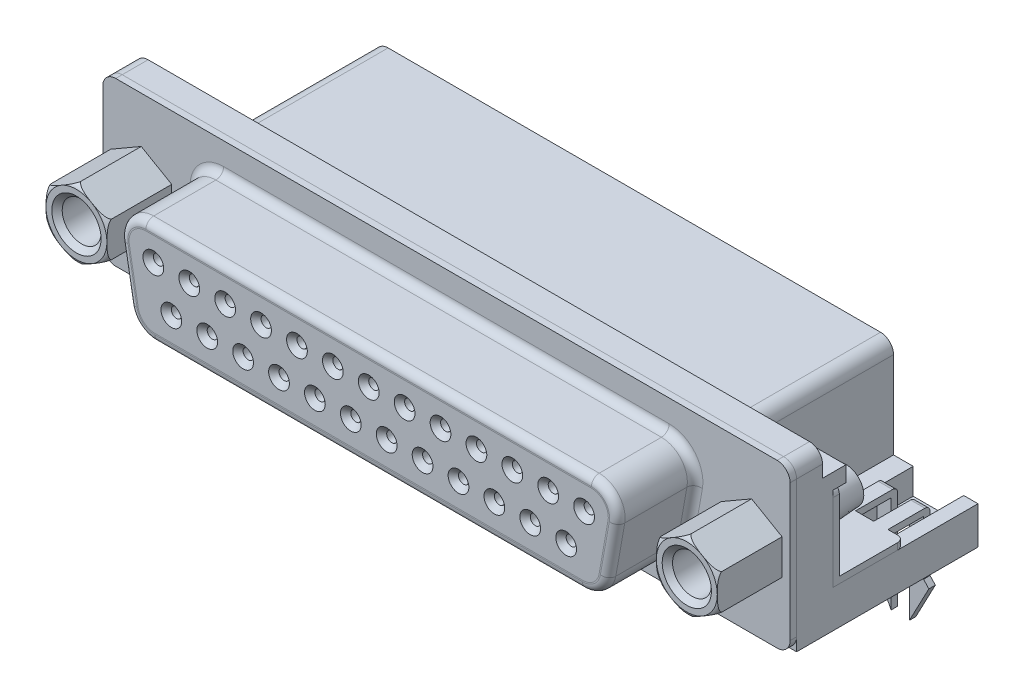
SolidWorks part; units mm, degrees
ref_plane "Alzado" through (0, 0, 0) normal (0, 0, 1) x (1, 0, 0)
ref_plane "Planta" through (0, 0, 0) normal (0, 1, 0) x (1, 0, 0)
ref_plane "Vista lateral" through (0, 0, 0) normal (1, 0, 0) x (0, 0, -1)
sketch "Croquis1" plane through (0, 0, 0) normal (0, 0, 1) x (1, 0, 0)
  line L1 (-25.52, 6.275) -> (25.52, 6.275)
  line L2 (-26.52, 5.275) -> (-26.52, -5.275)
  line L3 (-25.52, -6.275) -> (25.52, -6.275)
  line L4 (26.52, 5.275) -> (26.52, -5.275)
  arc A0 (25.52, 6.275) -> (26.52, 5.275) centre (25.52, 5.275) cw
  arc A1 (25.52, -6.275) -> (26.52, -5.275) centre (25.52, -5.275) ccw
  arc A2 (-25.52, 6.275) -> (-26.52, 5.275) centre (-25.52, 5.275) ccw
  arc A3 (-26.52, -5.275) -> (-25.52, -6.275) centre (-25.52, -5.275) ccw
  point P7 (26.52, 6.275)
  point P12 (-26.52, 6.275)
  dimension "D5" = 1
  dimension "D1" = 53.04
  dimension "D2" = 12.55
  dimension "D3" = 26.52
  dimension "D4" = 6.275
extrude "Extruir1" add sketch "Croquis1" along normal blind 0.5
sketch "Croquis2" plane through (0, 0, 0.5) normal (0, 0, 1) x (1, 0, 0)
  line L0 (19.1596, 1.6027) -> (18.4719, -2.2973)
  line L1 (-17.19, 3.95) -> (17.19, 3.95)
  line L2 (0, 0) -> (0, -16.7466) construction
  line L3 (-16.5023, -3.95) -> (16.5023, -3.95)
  line L4 (-19.1596, 1.6027) -> (-18.4719, -2.2973)
  arc A0 (19.1596, 1.6027) -> (17.19, 3.95) centre (17.19, 1.95) ccw
  arc A1 (-16.5023, -3.95) -> (-18.4719, -2.2973) centre (-16.5023, -1.95) cw
  arc A2 (-19.1596, 1.6027) -> (-17.19, 3.95) centre (-17.19, 1.95) cw
  arc A3 (16.5023, -3.95) -> (18.4719, -2.2973) centre (16.5023, -1.95) ccw
  dimension "D5" = 4
  dimension "D3" = 7.9
  dimension "D4" = 3.95
extrude "Extruir2" add sketch "Croquis2" along normal blind 6
sketch "Croquis3" plane through (0, 0, 6.5) normal (0, 0, 1) x (1, 0, 0)
  line L0 (17.19, 3.25) -> (-17.19, 3.25)
  line L1 (-18.4703, 1.7243) -> (-17.7826, -2.1757)
  line L2 (-16.5023, -3.25) -> (16.5023, -3.25)
  line L3 (17.7826, -2.1757) -> (18.4703, 1.7243)
  arc A0 (-17.19, 3.25) -> (-18.4703, 1.7243) centre (-17.19, 1.95) ccw
  arc A1 (-17.7826, -2.1757) -> (-16.5023, -3.25) centre (-16.5023, -1.95) ccw
  arc A2 (16.5023, -3.25) -> (17.7826, -2.1757) centre (16.5023, -1.95) ccw
  arc A3 (18.4703, 1.7243) -> (17.19, 3.25) centre (17.19, 1.95) ccw
extrude "Cortar-Extruir1" cut sketch "Croquis3" against normal blind 6
fillet "Redondeo1" radius 0.6 16 edges at (18.7221, 3.2356, 0.5) (18.8158, -0.3473, 0.5) (17.7879, -3.4821, 0.5) (0, -3.95, 0.5) (-17.7879, -3.4821, 0.5) (-18.8158, -0.3473, 0.5) (-18.7221, 3.2356, 0.5) (18.7221, 3.2356, 6.5) (18.8158, -0.3473, 6.5) (17.7879, -3.4821, 6.5) (0, -3.95, 6.5) (-17.7879, -3.4821, 6.5) (-18.8158, -0.3473, 6.5) (-18.7221, 3.2356, 6.5) (0, 3.95, 0.5) (0, 3.95, 6.5)
sketch "Croquis5" plane through (0, 0, 0.5) normal (0, 0, 1) x (1, 0, 0)
  line L4 (17.19, 3.25) -> (-17.19, 3.25)
  line L5 (-18.4703, 1.7243) -> (-17.7826, -2.1757)
  line L6 (-16.5023, -3.25) -> (16.5023, -3.25)
  line L7 (17.7826, -2.1757) -> (18.4703, 1.7243)
  line L8 (17.19, 3.25) -> (-17.19, 3.25)
  line L9 (-18.4703, 1.7243) -> (-17.7826, -2.1757)
  line L10 (-16.5023, -3.25) -> (16.5023, -3.25)
  line L11 (17.7826, -2.1757) -> (18.4703, 1.7243)
  circle A0 centre (16.625, 1.42) radius 0.4
  circle A1 centre (13.855, 1.42) radius 0.4
  circle A2 centre (11.085, 1.42) radius 0.4
  circle A3 centre (8.315, 1.42) radius 0.4
  arc A4 (18.4703, 1.7243) -> (17.19, 3.25) centre (17.19, 1.95) ccw
  arc A5 (-17.19, 3.25) -> (-18.4703, 1.7243) centre (-17.19, 1.95) ccw
  arc A6 (-17.7826, -2.1757) -> (-16.5023, -3.25) centre (-16.5023, -1.95) ccw
  arc A7 (16.5023, -3.25) -> (17.7826, -2.1757) centre (16.5023, -1.95) ccw
  arc A8 (18.4703, 1.7243) -> (17.19, 3.25) centre (17.19, 1.95) ccw
  arc A9 (-17.19, 3.25) -> (-18.4703, 1.7243) centre (-17.19, 1.95) ccw
  arc A10 (-17.7826, -2.1757) -> (-16.5023, -3.25) centre (-16.5023, -1.95) ccw
  arc A11 (16.5023, -3.25) -> (17.7826, -2.1757) centre (16.5023, -1.95) ccw
  circle A12 centre (5.545, 1.42) radius 0.4
  circle A13 centre (2.775, 1.42) radius 0.4
  circle A14 centre (0.005, 1.42) radius 0.4
  circle A15 centre (-2.765, 1.42) radius 0.4
  circle A16 centre (-5.535, 1.42) radius 0.4
  circle A17 centre (-8.305, 1.42) radius 0.4
  circle A18 centre (-11.075, 1.42) radius 0.4
  circle A19 centre (-13.845, 1.42) radius 0.4
  circle A20 centre (-16.615, 1.42) radius 0.4
  circle A21 centre (15.24, -1.42) radius 0.4
  circle A22 centre (12.47, -1.42) radius 0.4
  circle A23 centre (9.7, -1.42) radius 0.4
  circle A24 centre (6.93, -1.42) radius 0.4
  circle A25 centre (4.16, -1.42) radius 0.4
  circle A26 centre (1.39, -1.42) radius 0.4
  circle A27 centre (-1.38, -1.42) radius 0.4
  circle A28 centre (-4.15, -1.42) radius 0.4
  circle A29 centre (-6.92, -1.42) radius 0.4
  circle A30 centre (-9.69, -1.42) radius 0.4
  circle A31 centre (-12.46, -1.42) radius 0.4
  circle A32 centre (-15.23, -1.42) radius 0.4
  dimension "D2" = 0.8
  dimension "D3" = 16.625
  dimension "D4" = 1.42
  dimension "D1" = 0
extrude "Extruir3" add sketch "Croquis5" along normal blind 6 separate body
chamfer "Chaflán1" distance 0.4 angle 45 25 edges at (17.025, 1.42, 6.5) (14.255, 1.42, 6.5) (15.64, -1.42, 6.5) (12.87, -1.42, 6.5) (10.1, -1.42, 6.5) (11.485, 1.42, 6.5) (8.715, 1.42, 6.5) (5.945, 1.42, 6.5) (7.33, -1.42, 6.5) (4.56, -1.42, 6.5) (3.175, 1.42, 6.5) (0.405, 1.42, 6.5) (1.79, -1.42, 6.5) (-0.98, -1.42, 6.5) (-2.365, 1.42, 6.5) (-5.135, 1.42, 6.5) (-3.75, -1.42, 6.5) (-6.52, -1.42, 6.5) (-7.905, 1.42, 6.5) (-9.29, -1.42, 6.5) (-10.675, 1.42, 6.5) (-13.445, 1.42, 6.5) (-12.06, -1.42, 6.5) (-14.83, -1.42, 6.5) (-16.215, 1.42, 6.5)
sketch "Croquis6" plane through (0, 0, 0.5) normal (0, 0, 1) x (1, 0, 0)
  circle A0 centre (23.55, 0) radius 1.6
  circle A1 centre (-23.55, 0) radius 1.6
  dimension "D1" = 3.2
  dimension "D2" = 3.2
  dimension "D3" = 23.55
  dimension "D4" = 47.1
extrude "Cortar-Extruir2" cut sketch "Croquis6" against normal blind 6
sketch "Croquis7" plane through (0, 0, 0.5) normal (0, 0, 1) x (1, 0, 0)
  line L1 (23.55, 2.7135) -> (21.2, 1.3568)
  line L2 (21.2, 1.3568) -> (21.2, -1.3568)
  line L3 (21.2, -1.3568) -> (23.55, -2.7135)
  line L4 (23.55, -2.7135) -> (25.9, -1.3568)
  line L5 (25.9, -1.3568) -> (25.9, 1.3568)
  line L6 (25.9, 1.3568) -> (23.55, 2.7135)
  circle A0 centre (23.55, 0) radius 2.35 construction
extrude "Extruir4" add sketch "Croquis7" along normal blind 5 separate body
ref_plane "Plano1" through (23.55, 0, 0) normal (1, 0, 0) x (0, 0, -1)
sketch "Croquis8" plane through (23.55, 0, 0) normal (1, 0, 0) x (0, 0, -1)
  line L0 (-5.5, 1.3568) -> (-5.5, 2.7135) construction
  line L1 (-5.5, 2.7135) -> (-0.5, 2.7135) construction
  line L2 (-5.163, 2.7135) -> (-5.163, 5.0853)
  line L3 (-5.163, 5.0853) -> (-6.4864, 5.0853)
  line L4 (-6.4864, 5.0853) -> (-6.1878, 2.35)
  line L5 (-6.1878, 2.35) -> (-5.5, 2.35)
  line L6 (0, 0) -> (1.3514, 0) construction
  arc A0 (-5.5, 2.35) -> (-5.163, 2.7135) centre (-4.9764, 2.2026) cw
  dimension "D1" = 2.35
revolve "Cortar-Revolución1" cut sketch "Croquis8" angle 360 about L6
sketch "Croquis9" plane through (0, 0, 5.5) normal (0, 0, 1) x (1, 0, 0)
  circle A0 centre (23.55, 0) radius 1.5
  dimension "D1" = 3
extrude "Cortar-Extruir3" cut sketch "Croquis9" against normal blind 4
chamfer "Chaflán2" distance 0.4 angle 45 1 edges at (25.05, 0, 5.5)
mirror "Simetría1" about plane through (0, 0, 0) normal (1, 0, 0) of bodies 108
sketch "Croquis10" plane through (0, 0, 0) normal (0, 0, -1) x (-1, 0, 0)
  line L1 (-25.52, 6.275) -> (25.52, 6.275)
  line L2 (-26.52, 5.275) -> (-26.52, -6.275)
  line L3 (-26.52, -6.275) -> (26.52, -6.275)
  line L4 (26.52, 5.275) -> (26.52, -6.275)
  arc A0 (-25.52, 6.275) -> (-26.52, 5.275) centre (-25.52, 5.275) ccw
  arc A1 (25.52, 6.275) -> (26.52, 5.275) centre (25.52, 5.275) cw
  dimension "D1" = 1
extrude "Extruir5" add sketch "Croquis10" along normal blind 14 separate body
sketch "Croquis11" plane through (0, 0, -14) normal (0, 0, -1) x (-1, 0, 0)
  line L0 (30.0293, -3.375) -> (20, -3.375)
  line L1 (20, -3.375) -> (20, 4.325)
  line L2 (20, 4.325) -> (-20, 4.325)
  line L3 (-20, 4.325) -> (-20, -3.375)
  line L4 (-20, -3.375) -> (-30.6506, -3.375)
  line L5 (-30.6506, -3.375) -> (-30.6506, 10.8258)
  line L6 (-30.6506, 10.8258) -> (30.0293, 10.8258)
  line L7 (30.0293, 10.8258) -> (30.0293, -3.375)
  line L8 (-26.52, -6.275) -> (26.52, -6.275) construction
  dimension "D1" = 40
  dimension "D2" = 20
  dimension "D3" = 2.9
  dimension "D4" = 2.9
  dimension "D5" = 7.7
extrude "Cortar-Extruir4" cut sketch "Croquis11" against normal blind 12
fillet "Redondeo2" radius 1 2 edges at (-20, 4.325, -8) (20, 4.325, -8)
sketch "Croquis12" plane through (26.52, 0, 0) normal (1, 0, 0) x (0, 0, -1)
  line L0 (2, 4.325) -> (3.8, 4.325)
  line L1 (2, 4.325) -> (14, 4.325) construction
  line L2 (3.8, 4.325) -> (3.8, 3.125)
  line L3 (3.8, 3.125) -> (2.8, 3.125)
  line L4 (2.8, 3.125) -> (2.8, -3.375)
  line L5 (14, -3.375) -> (2, -3.375) construction
  line L6 (2.8, -3.375) -> (2, -3.375)
  line L7 (2, -3.375) -> (2, 4.325)
  dimension "D1" = 1.8
  dimension "D2" = 1
  dimension "D3" = 1.2
extrude "Extruir6" add sketch "Croquis12" against normal up to surface (53.04 mm away) separate body up to face at (-26.52, -1.4583, -5.3333)
combine bodies "Combinar1" operation type add bodies to combine 111 112
sketch "Croquis13" plane through (0, -3.375, 0) normal (0, 1, 0) x (-1, 0, 0)
  line L0 (-20, -2.8) -> (-26.52, -2.8) construction
  line L1 (-25.42, -2.8) -> (-21.52, -2.8)
  line L2 (-25.42, -2.8) -> (-25.42, -16.797)
  line L3 (-25.42, -16.797) -> (-21.52, -16.797)
  line L4 (-21.52, -2.8) -> (-21.52, -16.797)
  line L5 (-26.52, -14) -> (-26.52, -2.8) construction
  line L6 (0, 0) -> (0, -26.0275) construction
  line L7 (21.52, -2.8) -> (21.52, -16.797)
  line L8 (25.42, -16.797) -> (21.52, -16.797)
  line L9 (25.42, -2.8) -> (25.42, -16.797)
  line L10 (25.42, -2.8) -> (21.52, -2.8)
  dimension "D1" = 1.1
  dimension "D2" = 3.9
extrude "Cortar-Extruir5" cut sketch "Croquis13" against normal blind 2
sketch "Croquis14" plane through (0, -6.275, 0) normal (0, -1, 0) x (1, 0, 0)
  line L0 (21.52, -14) -> (25.42, -14) construction
  line L1 (19.75, -15.6683) -> (-19.75, -15.6683)
  line L2 (19.75, -15.6683) -> (19.75, -2)
  line L3 (19.75, -2) -> (-19.75, -2)
  line L4 (-19.75, -15.6683) -> (-19.75, -2)
  point P4 (23.47, -14)
  dimension "D1" = 39.5
  dimension "D2" = 12
  dimension "D3" = 19.75
extrude "Cortar-Extruir6" cut sketch "Croquis14" against normal blind 0.6
sketch "Croquis15" plane through (0, -5.675, 0) normal (0, -1, 0) x (1, 0, 0)
  line L0 (16.975, -12.35) -> (16.275, -12.35) construction
  line L1 (16.975, -12) -> (16.275, -12)
  line L2 (16.975, -12) -> (16.975, -12.7)
  line L3 (16.975, -12.7) -> (16.275, -12.7)
  line L4 (16.275, -12) -> (16.275, -12.7)
  line L5 (16.625, -12) -> (16.625, -12.7) construction
  line L6 (19.75, -14) -> (-19.75, -14) construction
  line L7 (14.205, -12) -> (13.505, -12)
  line L8 (14.205, -12) -> (14.205, -12.7)
  line L9 (14.205, -12.7) -> (13.505, -12.7)
  line L10 (13.505, -12) -> (13.505, -12.7)
  line L11 (14.205, -12.35) -> (13.505, -12.35) construction
  line L12 (13.855, -12) -> (13.855, -12.7) construction
  line L13 (11.435, -12) -> (10.735, -12)
  line L14 (11.435, -12) -> (11.435, -12.7)
  line L15 (11.435, -12.7) -> (10.735, -12.7)
  line L16 (10.735, -12) -> (10.735, -12.7)
  line L17 (11.435, -12.35) -> (10.735, -12.35) construction
  line L18 (11.085, -12) -> (11.085, -12.7) construction
  line L19 (8.665, -12) -> (7.965, -12)
  line L20 (8.665, -12) -> (8.665, -12.7)
  line L21 (8.665, -12.7) -> (7.965, -12.7)
  line L22 (7.965, -12) -> (7.965, -12.7)
  line L23 (8.665, -12.35) -> (7.965, -12.35) construction
  line L24 (8.315, -12) -> (8.315, -12.7) construction
  line L25 (5.895, -12) -> (5.195, -12)
  line L26 (5.895, -12) -> (5.895, -12.7)
  line L27 (5.895, -12.7) -> (5.195, -12.7)
  line L28 (5.195, -12) -> (5.195, -12.7)
  line L29 (5.895, -12.35) -> (5.195, -12.35) construction
  line L30 (5.545, -12) -> (5.545, -12.7) construction
  line L31 (3.125, -12) -> (2.425, -12)
  line L32 (3.125, -12) -> (3.125, -12.7)
  line L33 (3.125, -12.7) -> (2.425, -12.7)
  line L34 (2.425, -12) -> (2.425, -12.7)
  line L35 (3.125, -12.35) -> (2.425, -12.35) construction
  line L36 (2.775, -12) -> (2.775, -12.7) construction
  line L37 (0.355, -12) -> (-0.345, -12)
  line L38 (0.355, -12) -> (0.355, -12.7)
  line L39 (0.355, -12.7) -> (-0.345, -12.7)
  line L40 (-0.345, -12) -> (-0.345, -12.7)
  line L41 (0.355, -12.35) -> (-0.345, -12.35) construction
  line L42 (0.005, -12) -> (0.005, -12.7) construction
  line L43 (-2.415, -12) -> (-3.115, -12)
  line L44 (-2.415, -12) -> (-2.415, -12.7)
  line L45 (-2.415, -12.7) -> (-3.115, -12.7)
  line L46 (-3.115, -12) -> (-3.115, -12.7)
  line L47 (-2.415, -12.35) -> (-3.115, -12.35) construction
  line L48 (-2.765, -12) -> (-2.765, -12.7) construction
  line L49 (-5.185, -12) -> (-5.885, -12)
  line L50 (-5.185, -12) -> (-5.185, -12.7)
  line L51 (-5.185, -12.7) -> (-5.885, -12.7)
  line L52 (-5.885, -12) -> (-5.885, -12.7)
  line L53 (-5.185, -12.35) -> (-5.885, -12.35) construction
  line L54 (-5.535, -12) -> (-5.535, -12.7) construction
  line L55 (-7.955, -12) -> (-8.655, -12)
  line L56 (-7.955, -12) -> (-7.955, -12.7)
  line L57 (-7.955, -12.7) -> (-8.655, -12.7)
  line L58 (-8.655, -12) -> (-8.655, -12.7)
  line L59 (-7.955, -12.35) -> (-8.655, -12.35) construction
  line L60 (-8.305, -12) -> (-8.305, -12.7) construction
  line L61 (-10.725, -12) -> (-11.425, -12)
  line L62 (-10.725, -12) -> (-10.725, -12.7)
  line L63 (-10.725, -12.7) -> (-11.425, -12.7)
  line L64 (-11.425, -12) -> (-11.425, -12.7)
  line L65 (-10.725, -12.35) -> (-11.425, -12.35) construction
  line L66 (-11.075, -12) -> (-11.075, -12.7) construction
  line L67 (-13.495, -12) -> (-14.195, -12)
  line L68 (-13.495, -12) -> (-13.495, -12.7)
  line L69 (-13.495, -12.7) -> (-14.195, -12.7)
  line L70 (-14.195, -12) -> (-14.195, -12.7)
  line L71 (-13.495, -12.35) -> (-14.195, -12.35) construction
  line L72 (-13.845, -12) -> (-13.845, -12.7) construction
  line L73 (-16.265, -12) -> (-16.965, -12)
  line L74 (-16.265, -12) -> (-16.265, -12.7)
  line L75 (-16.265, -12.7) -> (-16.965, -12.7)
  line L76 (-16.965, -12) -> (-16.965, -12.7)
  line L77 (-16.265, -12.35) -> (-16.965, -12.35) construction
  line L78 (-16.615, -12) -> (-16.615, -12.7) construction
  line L79 (15.59, -9.86) -> (14.89, -9.86)
  line L80 (15.59, -9.16) -> (15.59, -9.86)
  line L81 (15.24, -9.16) -> (15.24, -9.86) construction
  line L82 (15.59, -9.51) -> (14.89, -9.51) construction
  line L83 (15.59, -9.16) -> (14.89, -9.16)
  line L84 (14.89, -9.16) -> (14.89, -9.86)
  line L85 (12.82, -9.86) -> (12.12, -9.86)
  line L86 (12.82, -9.16) -> (12.82, -9.86)
  line L87 (12.82, -9.16) -> (12.12, -9.16)
  line L88 (12.12, -9.16) -> (12.12, -9.86)
  line L89 (12.47, -9.16) -> (12.47, -9.86) construction
  line L90 (12.82, -9.51) -> (12.12, -9.51) construction
  line L91 (10.05, -9.86) -> (9.35, -9.86)
  line L92 (10.05, -9.16) -> (10.05, -9.86)
  line L93 (10.05, -9.16) -> (9.35, -9.16)
  line L94 (9.35, -9.16) -> (9.35, -9.86)
  line L95 (9.7, -9.16) -> (9.7, -9.86) construction
  line L96 (10.05, -9.51) -> (9.35, -9.51) construction
  line L97 (7.28, -9.86) -> (6.58, -9.86)
  line L98 (7.28, -9.16) -> (7.28, -9.86)
  line L99 (7.28, -9.16) -> (6.58, -9.16)
  line L100 (6.58, -9.16) -> (6.58, -9.86)
  line L101 (6.93, -9.16) -> (6.93, -9.86) construction
  line L102 (7.28, -9.51) -> (6.58, -9.51) construction
  line L103 (4.51, -9.86) -> (3.81, -9.86)
  line L104 (4.51, -9.16) -> (4.51, -9.86)
  line L105 (4.51, -9.16) -> (3.81, -9.16)
  line L106 (3.81, -9.16) -> (3.81, -9.86)
  line L107 (4.16, -9.16) -> (4.16, -9.86) construction
  line L108 (4.51, -9.51) -> (3.81, -9.51) construction
  line L109 (1.74, -9.86) -> (1.04, -9.86)
  line L110 (1.74, -9.16) -> (1.74, -9.86)
  line L111 (1.74, -9.16) -> (1.04, -9.16)
  line L112 (1.04, -9.16) -> (1.04, -9.86)
  line L113 (1.39, -9.16) -> (1.39, -9.86) construction
  line L114 (1.74, -9.51) -> (1.04, -9.51) construction
  line L115 (-1.03, -9.86) -> (-1.73, -9.86)
  line L116 (-1.03, -9.16) -> (-1.03, -9.86)
  line L117 (-1.03, -9.16) -> (-1.73, -9.16)
  line L118 (-1.73, -9.16) -> (-1.73, -9.86)
  line L119 (-1.38, -9.16) -> (-1.38, -9.86) construction
  line L120 (-1.03, -9.51) -> (-1.73, -9.51) construction
  line L121 (-3.8, -9.86) -> (-4.5, -9.86)
  line L122 (-3.8, -9.16) -> (-3.8, -9.86)
  line L123 (-3.8, -9.16) -> (-4.5, -9.16)
  line L124 (-4.5, -9.16) -> (-4.5, -9.86)
  line L125 (-4.15, -9.16) -> (-4.15, -9.86) construction
  line L126 (-3.8, -9.51) -> (-4.5, -9.51) construction
  line L127 (-6.57, -9.86) -> (-7.27, -9.86)
  line L128 (-6.57, -9.16) -> (-6.57, -9.86)
  line L129 (-6.57, -9.16) -> (-7.27, -9.16)
  line L130 (-7.27, -9.16) -> (-7.27, -9.86)
  line L131 (-6.92, -9.16) -> (-6.92, -9.86) construction
  line L132 (-6.57, -9.51) -> (-7.27, -9.51) construction
  line L133 (-9.34, -9.86) -> (-10.04, -9.86)
  line L134 (-9.34, -9.16) -> (-9.34, -9.86)
  line L135 (-9.34, -9.16) -> (-10.04, -9.16)
  line L136 (-10.04, -9.16) -> (-10.04, -9.86)
  line L137 (-9.69, -9.16) -> (-9.69, -9.86) construction
  line L138 (-9.34, -9.51) -> (-10.04, -9.51) construction
  line L139 (-12.11, -9.86) -> (-12.81, -9.86)
  line L140 (-12.11, -9.16) -> (-12.11, -9.86)
  line L141 (-12.11, -9.16) -> (-12.81, -9.16)
  line L142 (-12.81, -9.16) -> (-12.81, -9.86)
  line L143 (-12.46, -9.16) -> (-12.46, -9.86) construction
  line L144 (-12.11, -9.51) -> (-12.81, -9.51) construction
  line L145 (-14.88, -9.86) -> (-15.58, -9.86)
  line L146 (-14.88, -9.16) -> (-14.88, -9.86)
  line L147 (-14.88, -9.16) -> (-15.58, -9.16)
  line L148 (-15.58, -9.16) -> (-15.58, -9.86)
  line L149 (-15.23, -9.16) -> (-15.23, -9.86) construction
  line L150 (-14.88, -9.51) -> (-15.58, -9.51) construction
  dimension "D1" = 0.7
  dimension "D2" = 0.7
  dimension "D3" = 1.65
  dimension "D4" = 16.625
extrude "Extruir7" add sketch "Croquis15" along normal blind 4.4 and the other way blind 2 separate body
sketch "Croquis16" plane through (0, -5.675, 0) normal (0, -1, 0) x (1, 0, 0)
  line L0 (16.975, -12) -> (16.975, -16.0355)
  line L1 (16.975, -12) -> (16.275, -12)
  line L2 (16.275, -12) -> (16.275, -16.0355)
  line L3 (16.275, -16.0355) -> (16.975, -16.0355)
  line L4 (14.205, -12) -> (14.205, -16.0355)
  line L5 (15.59, -9.16) -> (14.89, -9.16)
  line L6 (15.59, -9.16) -> (15.59, -16.0355)
  line L7 (15.59, -16.0355) -> (14.89, -16.0355)
  line L8 (14.89, -9.16) -> (14.89, -16.0355)
  line L9 (14.205, -12) -> (13.505, -12)
  line L10 (13.505, -12) -> (13.505, -16.0355)
  line L11 (13.505, -16.0355) -> (14.205, -16.0355)
  line L12 (12.82, -9.16) -> (12.12, -9.16)
  line L13 (12.82, -9.16) -> (12.82, -16.0355)
  line L14 (12.82, -16.0355) -> (12.12, -16.0355)
  line L15 (12.12, -9.16) -> (12.12, -16.0355)
  line L16 (11.435, -12) -> (11.435, -16.0355)
  line L17 (11.435, -12) -> (10.735, -12)
  line L18 (10.735, -12) -> (10.735, -16.0355)
  line L19 (10.735, -16.0355) -> (11.435, -16.0355)
  line L20 (10.05, -9.16) -> (9.35, -9.16)
  line L21 (10.05, -9.16) -> (10.05, -16.0355)
  line L22 (10.05, -16.0355) -> (9.35, -16.0355)
  line L23 (9.35, -9.16) -> (9.35, -16.0355)
  line L24 (8.665, -12) -> (8.665, -16.0355)
  line L25 (8.665, -12) -> (7.965, -12)
  line L26 (7.965, -12) -> (7.965, -16.0355)
  line L27 (7.965, -16.0355) -> (8.665, -16.0355)
  line L28 (7.28, -9.16) -> (6.58, -9.16)
  line L29 (7.28, -9.16) -> (7.28, -16.0355)
  line L30 (7.28, -16.0355) -> (6.58, -16.0355)
  line L31 (6.58, -9.16) -> (6.58, -16.0355)
  line L32 (5.895, -12) -> (5.895, -16.0355)
  line L33 (5.895, -12) -> (5.195, -12)
  line L34 (5.195, -12) -> (5.195, -16.0355)
  line L35 (5.195, -16.0355) -> (5.895, -16.0355)
  line L36 (4.51, -9.16) -> (3.81, -9.16)
  line L37 (4.51, -9.16) -> (4.51, -16.0355)
  line L38 (4.51, -16.0355) -> (3.81, -16.0355)
  line L39 (3.81, -9.16) -> (3.81, -16.0355)
  line L40 (3.125, -12) -> (3.125, -16.0355)
  line L41 (3.125, -12) -> (2.425, -12)
  line L42 (2.425, -12) -> (2.425, -16.0355)
  line L43 (2.425, -16.0355) -> (3.125, -16.0355)
  line L44 (1.74, -9.16) -> (1.04, -9.16)
  line L45 (1.74, -9.16) -> (1.74, -16.0355)
  line L46 (1.74, -16.0355) -> (1.04, -16.0355)
  line L47 (1.04, -9.16) -> (1.04, -16.0355)
  line L48 (0.355, -12) -> (0.355, -16.0355)
  line L49 (0.355, -12) -> (-0.345, -12)
  line L50 (-0.345, -12) -> (-0.345, -16.0355)
  line L51 (-0.345, -16.0355) -> (0.355, -16.0355)
  line L52 (-1.03, -9.16) -> (-1.73, -9.16)
  line L53 (-1.03, -9.16) -> (-1.03, -16.0355)
  line L54 (-1.03, -16.0355) -> (-1.73, -16.0355)
  line L55 (-1.73, -9.16) -> (-1.73, -16.0355)
  line L56 (-2.415, -12) -> (-2.415, -16.0355)
  line L57 (-2.415, -12) -> (-3.115, -12)
  line L58 (-3.115, -12) -> (-3.115, -16.0355)
  line L59 (-3.115, -16.0355) -> (-2.415, -16.0355)
  line L60 (-3.8, -9.16) -> (-4.5, -9.16)
  line L61 (-3.8, -9.16) -> (-3.8, -16.0355)
  line L62 (-3.8, -16.0355) -> (-4.5, -16.0355)
  line L63 (-4.5, -9.16) -> (-4.5, -16.0355)
  line L64 (-5.185, -12) -> (-5.185, -16.0355)
  line L65 (-5.185, -12) -> (-5.885, -12)
  line L66 (-5.885, -12) -> (-5.885, -16.0355)
  line L67 (-5.885, -16.0355) -> (-5.185, -16.0355)
  line L68 (-6.57, -9.16) -> (-7.27, -9.16)
  line L69 (-6.57, -9.16) -> (-6.57, -16.0355)
  line L70 (-6.57, -16.0355) -> (-7.27, -16.0355)
  line L71 (-7.27, -9.16) -> (-7.27, -16.0355)
  line L72 (-7.955, -12) -> (-7.955, -16.0355)
  line L73 (-7.955, -12) -> (-8.655, -12)
  line L74 (-8.655, -12) -> (-8.655, -16.0355)
  line L75 (-8.655, -16.0355) -> (-7.955, -16.0355)
  line L76 (-9.34, -9.16) -> (-10.04, -9.16)
  line L77 (-9.34, -9.16) -> (-9.34, -16.0355)
  line L78 (-9.34, -16.0355) -> (-10.04, -16.0355)
  line L79 (-10.04, -9.16) -> (-10.04, -16.0355)
  line L80 (-10.725, -12) -> (-10.725, -16.0355)
  line L81 (-10.725, -12) -> (-11.425, -12)
  line L82 (-11.425, -12) -> (-11.425, -16.0355)
  line L83 (-11.425, -16.0355) -> (-10.725, -16.0355)
  line L84 (-12.11, -9.16) -> (-12.81, -9.16)
  line L85 (-12.11, -9.16) -> (-12.11, -16.0355)
  line L86 (-12.11, -16.0355) -> (-12.81, -16.0355)
  line L87 (-12.81, -9.16) -> (-12.81, -16.0355)
  line L88 (-13.495, -12) -> (-13.495, -16.0355)
  line L89 (-13.495, -12) -> (-14.195, -12)
  line L90 (-14.195, -12) -> (-14.195, -16.0355)
  line L91 (-14.195, -16.0355) -> (-13.495, -16.0355)
  line L92 (-14.88, -9.16) -> (-15.58, -9.16)
  line L93 (-14.88, -9.16) -> (-14.88, -16.0355)
  line L94 (-14.88, -16.0355) -> (-15.58, -16.0355)
  line L95 (-15.58, -9.16) -> (-15.58, -16.0355)
  line L97 (-16.265, -12) -> (-16.965, -12)
  line L98 (-16.265, -12) -> (-16.265, -16.0355)
  line L99 (-16.265, -16.0355) -> (-16.965, -16.0355)
  line L100 (-16.965, -12) -> (-16.965, -16.0355)
  dimension "D1" = 0.7
extrude "Cortar-Extruir7" cut sketch "Croquis16" against normal blind 2
sketch "Croquis17" plane through (0, -5.375, 0) normal (0, 1, 0) x (-1, 0, 0)
  line L0 (-25.42, -2.8) -> (-25.42, -14) construction
  line L1 (-21.52, -14) -> (-21.52, -2.8) construction
  line L2 (-21.52, -9.3) -> (-21.52, -11.3)
  line L3 (-25.42, -9.3) -> (-25.42, -11.3)
  line L4 (0, 0) -> (0, 17.0288) construction
  line L5 (25.42, -9.3) -> (25.42, -11.3)
  line L6 (21.52, -9.3) -> (21.52, -11.3)
  arc A0 (-25.42, -11.3) -> (-21.52, -11.3) centre (-23.47, -11.3) ccw
  arc A1 (21.52, -9.3) -> (25.42, -9.3) centre (23.47, -9.3) cw
  arc A2 (25.42, -11.3) -> (21.52, -11.3) centre (23.47, -11.3) cw
  arc A3 (-21.52, -9.3) -> (-25.42, -9.3) centre (-23.47, -9.3) ccw
  dimension "D1" = 11.8
extrude "Cortar-Extruir9" cut sketch "Croquis17" against normal blind 4
sketch "Croquis18" plane through (0, 0, -2.8) normal (0, 0, -1) x (-1, 0, 0)
  line L1 (-26.02, 3.125) -> (-21.0224, 3.125)
  line L2 (-26.52, 2.625) -> (-26.52, -3.375)
  line L3 (-26.52, -3.375) -> (-20.5224, -3.375)
  line L4 (-20.5224, 2.625) -> (-20.5224, -3.375)
  arc A0 (-26.02, 3.125) -> (-26.52, 2.625) centre (-26.02, 2.625) ccw
  arc A1 (-21.0224, 3.125) -> (-20.5224, 2.625) centre (-21.0224, 2.625) cw
  point P8 (-26.52, 3.125)
  dimension "D1" = 0.5
extrude "Extruir8" add sketch "Croquis18" along normal blind 0.5 separate body
sketch "Croquis19" plane through (0, -3.375, 0) normal (0, 1, 0) x (-1, 0, 0)
  line L0 (-26.52, -14) -> (-26.52, -2.8) construction
  line L1 (-20.5224, -3.3) -> (-26.52, -3.3)
  line L2 (-20.5224, -3.3) -> (-20.5224, -7.8)
  line L3 (-21.0224, -8.3) -> (-24.17, -8.3)
  line L4 (-26.52, -3.3) -> (-26.52, -7.8)
  line L5 (-25.27, -8.3) -> (-25.27, -11.55)
  line L6 (-25.27, -11.55) -> (-24.17, -11.55)
  line L7 (-24.17, -11.55) -> (-24.17, -8.3)
  line L8 (-24.17, -8.3) -> (-22.77, -8.3)
  line L9 (-22.77, -8.3) -> (-22.77, -11.55)
  line L10 (-22.77, -11.55) -> (-21.67, -11.55)
  line L11 (-21.67, -11.55) -> (-21.67, -8.3)
  line L12 (-25.52, 0.5) -> (-26.52, 0.5) construction
  line L13 (-21.52, -14) -> (-21.52, -2.8) construction
  line L14 (-25.42, -2.8) -> (-25.42, -14) construction
  line L15 (-25.27, -8.3) -> (-26.02, -8.3)
  line L16 (-21.67, -8.3) -> (-21.0224, -8.3)
  arc A0 (-26.02, -8.3) -> (-26.52, -7.8) centre (-26.02, -7.8) cw
  arc A1 (-20.5224, -7.8) -> (-21.0224, -8.3) centre (-21.0224, -7.8) cw
  point P9 (-26.52, -8.3)
  line M2 (-25.42, -14) -> (-25.42, -2.8)
  line M4 (-26.52, -2.8) -> (-26.52, -14)
  dimension "D2" = 0.5
  dimension "D1" = 5
  dimension "D3" = 12.05
  dimension "D4" = 0.15
  dimension "D5" = 0.15
  dimension "D6" = 1.1
  dimension "D7" = 1.1
extrude "Extruir9" add sketch "Croquis19" along normal blind 0.5 separate body contours A1 L2 L1 L15 L5 L6 L7 L3 M2 | A0 L15 L1 M2 M4 | L10 L11 L3 L9
combine bodies "Combinar2" operation type add bodies to combine 143 144
fillet "Redondeo3" radius 0.4 1 edges at (25.97, -3.375, -2.8)
sketch "Croquis20" plane through (0, 0, -11.55) normal (0, 0, -1) x (-1, 0, 0)
  line L0 (-25.27, -3.375) -> (-25.27, -7.5721)
  line L1 (-25.27, -7.5721) -> (-25.6775, -8.013)
  line L2 (-25.6775, -8.013) -> (-24.17, -10.875)
  line L3 (-24.17, -10.875) -> (-24.17, -3.375)
  line L4 (-25.27, -3.375) -> (-24.17, -3.375) construction
  line L5 (-24.17, -3.375) -> (-25.27, -3.375)
  line L6 (-25.27, -2.875) -> (-26.02, -2.875) construction
  line L7 (-23.47, -2.875) -> (-23.47, -7.5721) construction
  line L8 (-22.77, -2.875) -> (-24.17, -2.875) construction
  line L9 (-22.77, -3.375) -> (-21.67, -3.375)
  line L10 (-22.77, -10.875) -> (-22.77, -3.375)
  line L11 (-21.2625, -8.013) -> (-22.77, -10.875)
  line L12 (-21.67, -7.5721) -> (-21.2625, -8.013)
  line L13 (-21.67, -3.375) -> (-21.67, -7.5721)
  dimension "D1" = 8
extrude "Extruir10" add sketch "Croquis20" against normal blind 0.5 separate body
combine bodies "Combinar3" operation type add bodies to combine 146 147 145
fillet "Redondeo4" radius 0.4 2 edges at (22.22, -2.875, -11.55) (24.72, -2.875, -11.55)
sketch "Croquis21" plane through (0, 0, -3.3) normal (0, 0, -1) x (-1, 0, 0)
  circle A0 centre (-23.55, 0) radius 1.6
  dimension "D1" = 3.2
extrude "Extruir11" add sketch "Croquis21" along normal blind 3.5 draft 4 separate body
mirror "Simetría2" about plane through (0, 0, 0) normal (1, 0, 0) of bodies 149 148
sketch "Croquis22" plane through (0, 0, -14) normal (0, 0, -1) x (-1, 0, 0)
  line L0 (-18.4, 2.225) -> (18.4, 2.225)
  line L1 (-18.5, 2.325) -> (18.5, 2.325)
  line L2 (-18.5, 2.325) -> (-18.5, -3.675)
  line L3 (-18.5, -3.675) -> (18.5, -3.675)
  line L4 (18.5, 2.325) -> (18.5, -3.675)
  line L5 (18.4, 2.225) -> (18.4, -3.575)
  line L6 (-18.4, -3.575) -> (18.4, -3.575)
  line L7 (-18.4, 2.225) -> (-18.4, -3.575)
  dimension "D1" = 6
  dimension "D2" = 37
  dimension "D3" = 18.5
  dimension "D4" = 0.1
extrude "Cortar-Extruir10" cut sketch "Croquis22" against normal blind 6.5
